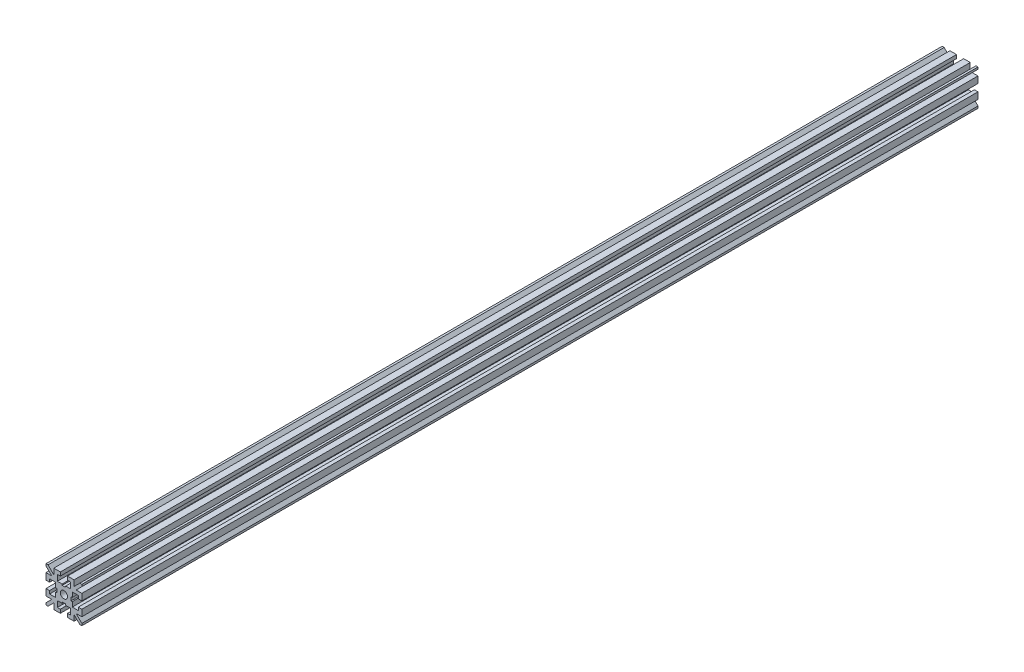
SolidWorks part; units mm, degrees
ref_plane "Front Plane" through (0, 0, 0) normal (0, 0, 1) x (1, 0, 0)
ref_plane "Top Plane" through (0, 0, 0) normal (0, 1, 0) x (1, 0, 0)
ref_plane "Right Plane" through (0, 0, 0) normal (1, 0, 0) x (0, 0, -1)
sketch "Sketch1" plane through (0, 0, 0) normal (0, 0, 1) x (1, 0, 0)
  line L1 (-9.0006, 3.7616) -> (5.9994, 3.7616)
  line L2 (-9.0006, 3.7616) -> (-9.0006, -11.2384)
  line L3 (-9.0006, -11.2384) -> (5.9994, -11.2384)
  line L4 (5.9994, 3.7616) -> (5.9994, -11.2384)
  dimension "D1" = 15
  dimension "D2" = 15
extrude "Boss-Extrude1" add sketch "Sketch1" along normal blind 375
sketch "Sketch2" plane through (0, 0, 375) normal (0, 0, 1) x (1, 0, 0)
  line L0 (-9.0006, 3.7616) -> (5.9994, -11.2384) construction
  line L1 (5.9994, 3.7616) -> (-9.0006, -11.2384) construction
  line L4 (1.9994, -4.4884) -> (1.9994, -6.4884)
  line L5 (5.9994, -3.7384) -> (1.9994, -3.7384) construction
  line L6 (5.9994, -11.2384) -> (5.9994, 3.7616) construction
  line L7 (-1.5006, 3.7616) -> (-1.5006, -3.7384) construction
  line L8 (5.9994, 3.7616) -> (-9.0006, 3.7616) construction
  line L9 (-9.0006, -3.7384) -> (-1.5006, -3.7384) construction
  line L10 (-9.0006, 3.7616) -> (-9.0006, -11.2384) construction
  line L11 (-1.5006, -11.2384) -> (-1.5006, -3.7384) construction
  line L12 (-9.0006, -11.2384) -> (5.9994, -11.2384) construction
  line L13 (1.9994, -4.4884) -> (1.4994, -4.4884)
  line L14 (1.9994, -0.9884) -> (4.4994, -0.9884)
  line L15 (1.9994, -0.9884) -> (1.9994, -2.9884)
  line L16 (1.9994, -6.4884) -> (4.4994, -6.4884)
  line L17 (4.4994, -0.9884) -> (4.4994, -6.4884)
  line L18 (-4.2506, -7.2384) -> (-4.2506, -9.7384)
  line L19 (1.9994, -2.9884) -> (1.4994, -2.9884)
  line L20 (1.4994, -4.4884) -> (1.4994, -2.9884)
  line L21 (1.4994, -3.7384) -> (-0.0006, -3.7384) construction
  line L22 (-2.2506, -7.2384) -> (-4.2506, -7.2384)
  line L23 (-2.2506, -7.2384) -> (-2.2506, -6.7384)
  line L24 (-2.2506, -6.7384) -> (-0.7506, -6.7384)
  line L25 (-0.7506, -7.2384) -> (-0.7506, -6.7384)
  line L26 (1.2494, -7.2384) -> (-0.7506, -7.2384)
  line L27 (1.2494, -7.2384) -> (1.2494, -9.7384)
  line L28 (1.2494, -9.7384) -> (-4.2506, -9.7384)
  line L29 (-5.0006, -0.9884) -> (-7.5006, -0.9884)
  line L30 (-5.0006, -2.9884) -> (-5.0006, -0.9884)
  line L31 (-5.0006, -2.9884) -> (-4.5006, -2.9884)
  line L32 (-4.5006, -2.9884) -> (-4.5006, -4.4884)
  line L33 (-5.0006, -4.4884) -> (-4.5006, -4.4884)
  line L34 (-5.0006, -6.4884) -> (-5.0006, -4.4884)
  line L35 (-5.0006, -6.4884) -> (-7.5006, -6.4884)
  line L36 (-7.5006, -6.4884) -> (-7.5006, -0.9884)
  line L37 (1.2494, -0.2384) -> (1.2494, 2.2616)
  line L38 (-0.7506, -0.2384) -> (1.2494, -0.2384)
  line L39 (-0.7506, -0.2384) -> (-0.7506, -0.7384)
  line L40 (-0.7506, -0.7384) -> (-2.2506, -0.7384)
  line L41 (-2.2506, -0.2384) -> (-2.2506, -0.7384)
  line L42 (-4.2506, -0.2384) -> (-2.2506, -0.2384)
  line L43 (-4.2506, -0.2384) -> (-4.2506, 2.2616)
  line L44 (-4.2506, 2.2616) -> (1.2494, 2.2616)
  circle A0 centre (-1.5006, -3.7384) radius 1.5
  point P60 (-1.5006, -3.7384)
  dimension "D1" = 5.5
  dimension "D2" = 2.5
  dimension "D3" = 1.5
  dimension "D4" = 2.75
  dimension "D5" = 0.5
  dimension "D6" = 1.5
  dimension "D7" = 0.75
  dimension "D8" = 4
extrude "Cut-Extrude1" cut sketch "Sketch2" against normal up to surface (375 mm away) up to face at (-1.5006, -3.7384, 0)
sketch "Sketch3" plane through (0, 0, 375) normal (0, 0, 1) x (1, 0, 0)
  line L0 (5.9994, 3.7616) -> (-9.0006, -11.2384) construction
  line L1 (-9.0006, 3.7616) -> (5.9994, -11.2384) construction
  line L2 (5.1509, 3.7616) -> (2.7494, 1.3602)
  line L3 (5.9994, 3.7616) -> (-9.0006, 3.7616) construction
  line L4 (2.7494, 1.3602) -> (2.7494, 3.7616)
  line L5 (2.7494, 3.7616) -> (5.1509, 3.7616)
  line L6 (1.2494, -0.2384) -> (1.2494, 2.2616) construction
  line L7 (5.9994, 0.5116) -> (5.9994, 2.9131)
  line L8 (3.5979, 0.5116) -> (5.9994, 0.5116)
  line L9 (5.9994, 2.9131) -> (3.5979, 0.5116)
  line L10 (1.2494, 2.2616) -> (-4.2506, 2.2616) construction
  line L11 (-3.0006, 3.7616) -> (-0.0006, 3.7616)
  line L12 (-3.0006, 3.7616) -> (-3.0006, 2.2616)
  line L13 (-3.0006, 2.2616) -> (-0.0006, 2.2616)
  line L14 (-0.0006, 3.7616) -> (-0.0006, 2.2616)
  line L15 (-2.2506, -0.7384) -> (-0.7506, -0.7384) construction
  line L16 (2.7494, -8.8369) -> (2.7494, -11.2384)
  line L17 (2.7494, -11.2384) -> (5.1509, -11.2384)
  line L18 (5.1509, -11.2384) -> (2.7494, -8.8369)
  line L19 (5.9994, -10.3898) -> (3.5979, -7.9884)
  line L20 (3.5979, -7.9884) -> (5.9994, -7.9884)
  line L21 (5.9994, -7.9884) -> (5.9994, -10.3898)
  line L22 (5.9994, -5.2384) -> (4.4994, -5.2384)
  line L23 (5.9994, -2.2384) -> (5.9994, -5.2384)
  line L24 (5.9994, -2.2384) -> (4.4994, -2.2384)
  line L25 (4.4994, -2.2384) -> (4.4994, -5.2384)
  line L26 (-6.5991, -7.9884) -> (-9.0006, -7.9884)
  line L27 (-9.0006, -7.9884) -> (-9.0006, -10.3898)
  line L28 (-9.0006, -10.3898) -> (-6.5991, -7.9884)
  line L29 (-8.1521, -11.2384) -> (-5.7506, -8.8369)
  line L30 (-5.7506, -8.8369) -> (-5.7506, -11.2384)
  line L31 (-5.7506, -11.2384) -> (-8.1521, -11.2384)
  line L32 (-3.0006, -11.2384) -> (-3.0006, -9.7384)
  line L33 (-0.0006, -11.2384) -> (-3.0006, -11.2384)
  line L34 (-0.0006, -11.2384) -> (-0.0006, -9.7384)
  line L35 (-0.0006, -9.7384) -> (-3.0006, -9.7384)
  line L36 (-5.7506, 1.3602) -> (-5.7506, 3.7616)
  line L37 (-5.7506, 3.7616) -> (-8.1521, 3.7616)
  line L38 (-8.1521, 3.7616) -> (-5.7506, 1.3602)
  line L39 (-9.0006, 2.9131) -> (-6.5991, 0.5116)
  line L40 (-6.5991, 0.5116) -> (-9.0006, 0.5116)
  line L41 (-9.0006, 0.5116) -> (-9.0006, 2.9131)
  line L42 (-9.0006, -2.2384) -> (-7.5006, -2.2384)
  line L43 (-9.0006, -5.2384) -> (-9.0006, -2.2384)
  line L44 (-9.0006, -5.2384) -> (-7.5006, -5.2384)
  line L45 (-7.5006, -5.2384) -> (-7.5006, -2.2384)
  point P24 (-1.5006, -0.7384)
  point P27 (-1.5006, -3.7384)
  point P61 (-1.5006, -3.7384)
  dimension "D1" = 0.6
  dimension "D2" = 1.5
  dimension "D3" = 3
  dimension "D4" = 1.5
  dimension "D5" = 4
extrude "Cut-Extrude2" cut sketch "Sketch3" against normal up to surface (375 mm away) up to face at (-1.5006, 0.2616, 0)
